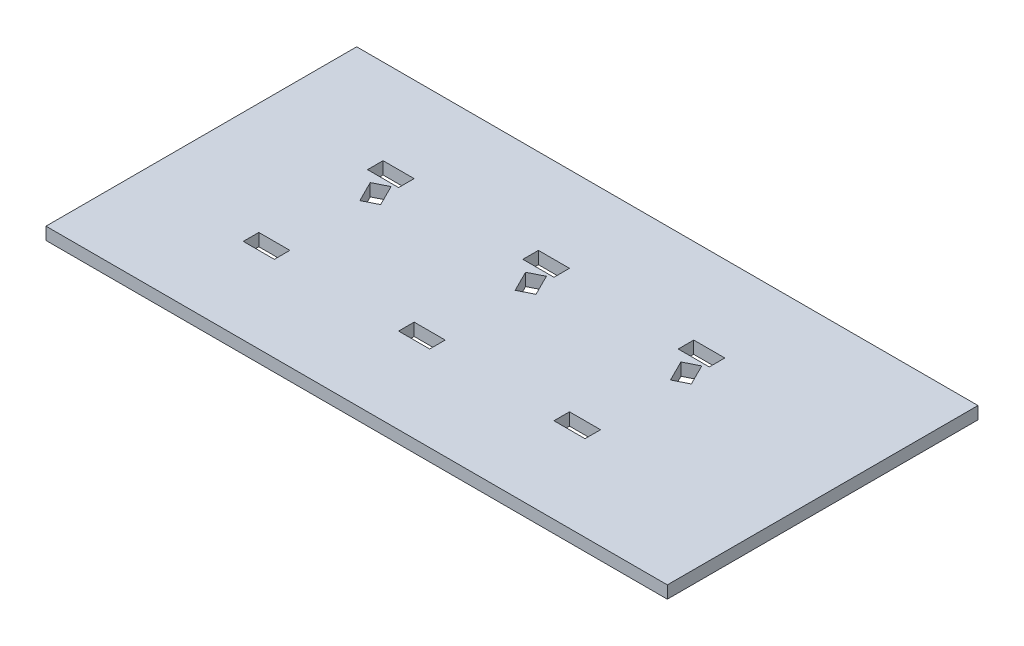
SolidWorks part; units mm, degrees
ref_plane "Front Plane" through (0, 0, 0) normal (0, 0, 1) x (1, 0, 0)
ref_plane "Top Plane" through (0, 0, 0) normal (0, 1, 0) x (1, 0, 0)
ref_plane "Right Plane" through (0, 0, 0) normal (1, 0, 0) x (0, 0, -1)
sketch "Sketch1" plane through (0, 0, 0) normal (0, 1, 0) x (1, 0, 0)
  line L1 (-50.8, -25.4) -> (50.8, -25.4)
  line L2 (-50.8, -25.4) -> (-50.8, 25.4)
  line L3 (-50.8, 25.4) -> (50.8, 25.4)
  line L4 (50.8, -25.4) -> (50.8, 25.4)
  line L5 (0, 25.4) -> (0, -25.4) construction
  line L6 (-50.8, 0) -> (50.8, 0) construction
  point P0 (0, 0)
  dimension "D1" = 50.8
  dimension "D2" = 101.6
extrude "Boss-Extrude1" add sketch "Sketch1" along normal blind 2.032
sketch "Sketch2" plane through (0, 2.032, 0) normal (0, 1, 0) x (1, 0, 0)
  line L0 (-3.3577, 3.8746) -> (-1.0859, 5.0107)
  line L1 (-3.3577, 3.8746) -> (-5.0618, 7.2822)
  line L2 (-1.0859, 5.0107) -> (-2.7901, 8.4183)
  line L3 (-5.0618, 7.2822) -> (-2.7901, 8.4183)
  line L5 (-1.1176, 0) -> (1.1176, 0) construction
  circle A0 centre (0, 0) radius 5.127 construction
  dimension "D1" = 10.254
  dimension "D3" = 3.81
  dimension "D4" = 2.54
  dimension "D2" = 63.43
extrude "Cut-Extrude1" cut sketch "Sketch2" against normal through all contours L3 L1 L0 L2 region at (-3.0739, 2.032, -6.1464)
sketch "Sketch3" plane through (0, 2.032, 0) normal (0, 1, 0) x (1, 0, 0)
  line L0 (-7.112, 8.89) -> (-2.032, 8.89)
  line L1 (-7.112, 8.89) -> (-7.112, 11.43)
  line L2 (-2.032, 8.89) -> (-2.032, 11.43)
  line L3 (-7.112, 11.43) -> (-2.032, 11.43)
  line L4 (-1.1176, 0) -> (1.1176, 0) construction
  line L5 (0, -1.1176) -> (0, 1.1176) construction
  dimension "D1" = 2.54
  dimension "D2" = 5.08
  dimension "D3" = 2.032
  dimension "D4" = 8.89
extrude "Cut-Extrude2" cut sketch "Sketch3" against normal through all
mirror "Mirror1" about plane through (0, 0, 0) normal (0, 0, 1) of "Cut-Extrude2"
pattern_linear "LPattern1" count 2 spacing 25.4 along (-1, 0, 0) count 2 spacing 25.4 along (1, 0, 0) of "Cut-Extrude1", "Cut-Extrude2", "Mirror1"
equation "\"Arrow Height\"= 1in"
equation "\"Button Height\"= 2in"
equation "\"Button Width\"= 4in"
equation "\"Haptic Diameter\"= 10mm"
equation "\"Haptic Thickness\"= 2.7mm"
equation "\"D1@Sketch1\"=\"Button Height\""
equation "\"D2@Sketch1\"=\"Button Width\""
equation "\"D1@Sketch2\"=\"Haptic Diameter\"+.01in"
